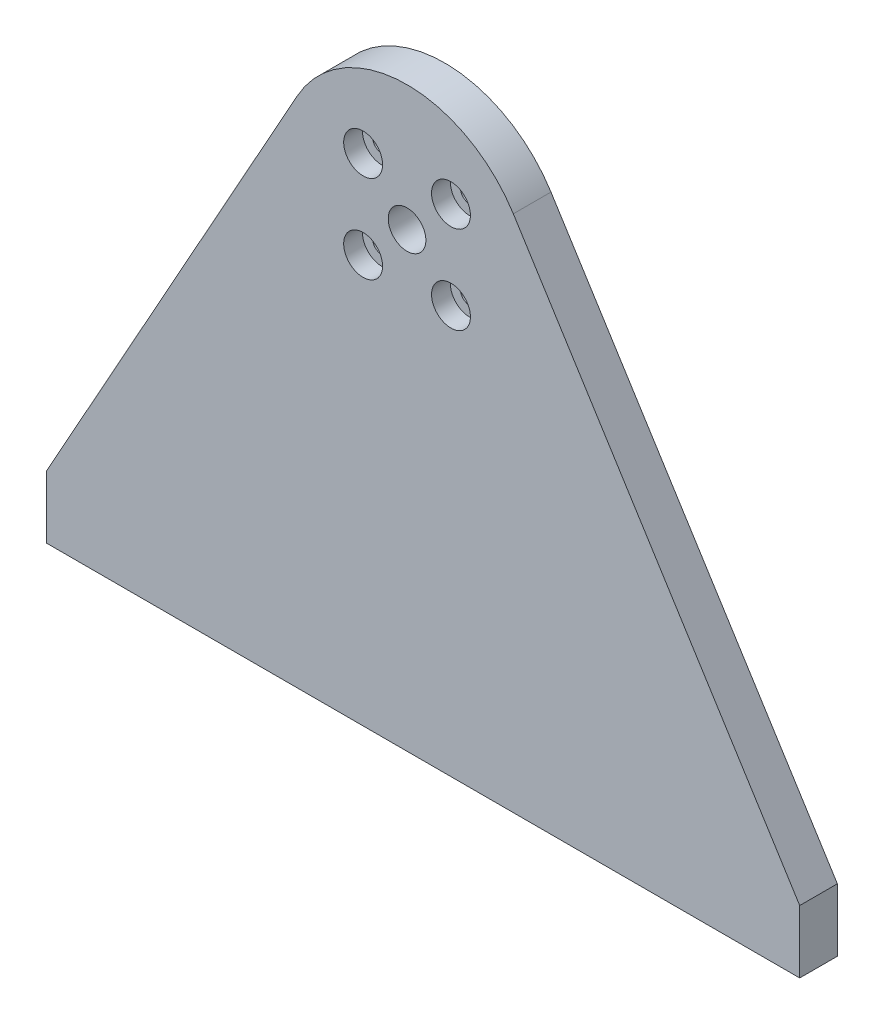
SolidWorks part; units mm, degrees
ref_plane "前视基准面" through (0, 0, 0) normal (0, 0, 1) x (1, 0, 0)
ref_plane "上视基准面" through (0, 0, 0) normal (0, 1, 0) x (1, 0, 0)
ref_plane "右视基准面" through (0, 0, 0) normal (1, 0, 0) x (0, 0, -1)
other "Configuration Table"
sketch "草图1" plane through (0, 0, 0) normal (0, 0, 1) x (1, 0, 0)
  line L5 (53.2118, 15.1053) -> (98.8463, -57.534)
  line L6 (18.8044, 14.1987) -> (-21.1537, -57.534)
  line L9 (98.8463, -57.534) -> (98.8463, -67.534)
  line L10 (98.8463, -67.534) -> (-21.1537, -67.534)
  line L11 (-21.1537, -67.534) -> (-21.1537, -57.534)
  arc A0 (53.2118, 15.1053) -> (18.8044, 14.1987) centre (36.2765, 4.466) ccw
  circle A2 centre (36.2765, 4.466) radius 3
  point P0 (0, 0)
  point P8 (98.8463, -57.534)
extrude "凸台-拉伸1" add sketch "草图1" along normal blind 6
sketch "草图2" plane through (0, 0, 6) normal (0, 0, 1) x (1, 0, 0)
  line L0 (36.2765, 4.466) -> (36.2765, 16.549) construction
  line L5 (36.2765, 4.466) -> (44.4343, 4.466) construction
  circle A2 centre (29.2765, 11.466) radius 3.1
  circle A3 centre (43.2765, 11.466) radius 3.1
  circle A4 centre (43.2765, -2.534) radius 3.1
  circle A5 centre (29.2765, -2.534) radius 3.1
extrude "切除-拉伸6" cut sketch "草图2" against normal blind 3
sketch "草图4" plane through (0, 0, 3) normal (0, 0, 1) x (1, 0, 0)
  circle A0 centre (43.2765, 11.466) radius 1.5 construction
  circle A1 centre (43.2765, 11.466) radius 1.5
  circle A2 centre (43.2765, -2.534) radius 1.5 construction
  circle A3 centre (43.2765, -2.534) radius 1.5
  circle A4 centre (29.2765, -2.534) radius 1.5 construction
  circle A5 centre (29.2765, -2.534) radius 1.5
  circle A6 centre (29.2765, 11.466) radius 1.5 construction
  circle A7 centre (29.2765, 11.466) radius 1.5
extrude "切除-拉伸7" cut sketch "草图4" against normal through all
